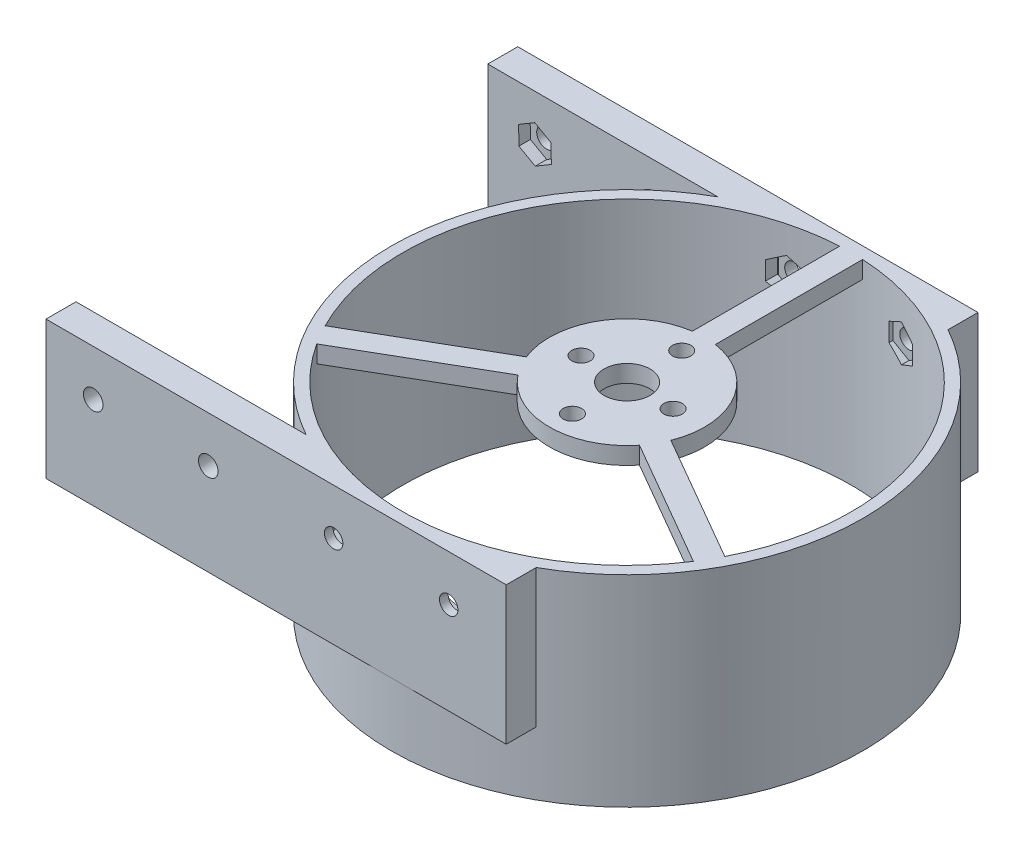
SolidWorks part; units mm, degrees
ref_plane "前视基准面" through (0, 0, 0) normal (0, 0, 1) x (1, 0, 0)
ref_plane "上视基准面" through (0, 0, 0) normal (0, 1, 0) x (1, 0, 0)
ref_plane "右视基准面" through (0, 0, 0) normal (1, 0, 0) x (0, 0, -1)
sketch "草图1" plane through (0, 0, 0) normal (0, 1, 0) x (1, 0, 0)
  circle A0 centre (0, 0) radius 39
  circle A1 centre (0, 0) radius 41
  dimension "D1" = 78
  dimension "D2" = 2
extrude "凸台-拉伸1" add sketch "草图1" along normal blind 20
sketch "草图2" plane through (0, 20, 0) normal (0, 1, 0) x (1, 0, 0)
  line L0 (20, -41) -> (-20, -41)
  line L1 (-20, -41) -> (-20, -35.7911)
  line L2 (0, -41) -> (0, -31.4417) construction
  line L3 (20, -41) -> (20, -35.7911)
  line L4 (0, 0) -> (26.2566, 0) construction
  line L5 (20, 41) -> (20, 35.7911)
  line L6 (20, 41) -> (-20, 41)
  line L7 (-20, 41) -> (-20, 35.7911)
  circle A0 centre (0, 0) radius 41 construction
  arc A1 (-20, -35.7911) -> (20, -35.7911) centre (0, 0) ccw
  arc A2 (-20, 35.7911) -> (20, 35.7911) centre (0, 0) cw
  circle M5 centre (0, 0) radius 41
extrude "凸台-拉伸2" add sketch "草图2" against normal blind 14 contours L1 L0 M5 | L0 L3 M5 region at (15.0657, 20, 39.4559) region at (-15.0657, 20, 39.4559)
sketch "草图3" plane through (0, 20, 0) normal (0, 1, 0) x (1, 0, 0)
  line L0 (-2, 38.9487) -> (-2, 13.351)
  line L1 (0, 39) -> (0, 13.5) construction
  line L2 (2, 38.9487) -> (2, 13.351)
  line L3 (34.7305, -17.7423) -> (12.5623, -4.9435)
  line L4 (32.7305, -21.2064) -> (10.5623, -8.4076)
  line L5 (-32.7305, -21.2064) -> (-10.5623, -8.4076)
  line L6 (-34.7305, -17.7423) -> (-12.5623, -4.9435)
  circle A0 centre (0, 0) radius 4
  circle A1 centre (-8, 0) radius 1.6
  circle A2 centre (8, 0) radius 1.6
  arc A3 (-10.5623, -8.4076) -> (10.5623, -8.4076) centre (0, 0) ccw
  circle A4 centre (0, 0) radius 39 construction
  arc A5 (2, 38.9487) -> (-2, 38.9487) centre (0, 0) ccw
  arc A6 (32.7305, -21.2064) -> (34.7305, -17.7423) centre (0, 0) ccw
  arc A7 (-34.7305, -17.7423) -> (-32.7305, -21.2064) centre (0, 0) ccw
  arc A8 (-2, 13.351) -> (-12.5623, -4.9435) centre (0, 0) ccw
  arc A9 (12.5623, -4.9435) -> (2, 13.351) centre (0, 0) ccw
  point P28 (0, 0)
  dimension "D1" = 8
  dimension "D2" = 3.2
  dimension "D3" = 8
  dimension "D4" = 3.2
  dimension "D5" = 8
  dimension "D6" = 27
  dimension "D7" = 2
  dimension "D8" = 3
extrude "凸台-拉伸3" add sketch "草图3" against normal blind 3
sketch "草图4" plane through (0, 0, 41) normal (0, 0, 1) x (1, 0, 0)
  line L0 (20, 20) -> (-20, 20) construction
  line L1 (-10, 8.7668) -> (-7.2, 10.3834)
  line L2 (-7.2, 10.3834) -> (-7.2, 13.6166)
  line L3 (-7.2, 13.6166) -> (-10, 15.2332)
  line L4 (-10, 15.2332) -> (-12.8, 13.6166)
  line L5 (-12.8, 13.6166) -> (-12.8, 10.3834)
  line L6 (-12.8, 10.3834) -> (-10, 8.7668)
  line L7 (0, 0) -> (0, -4.0742) construction
  line L8 (12.8, 10.3834) -> (10, 8.7668)
  line L9 (12.8, 13.6166) -> (12.8, 10.3834)
  line L10 (10, 15.2332) -> (12.8, 13.6166)
  line L11 (7.2, 13.6166) -> (10, 15.2332)
  line L12 (7.2, 10.3834) -> (7.2, 13.6166)
  line L13 (10, 8.7668) -> (7.2, 10.3834)
  circle A0 centre (-10, 12) radius 2.8 construction
  dimension "D1" = 5.6
  dimension "D2" = 10
  dimension "D3" = 8
sketch "草图7" plane through (0, 6, 0) normal (0, -1, 0) x (1, 0, 0)
  line L2 (-20, 41) -> (-20, 35.7911)
  line L3 (0, 41) -> (-20, 41)
  line L4 (-20, 41) -> (-20, 35.7911)
  line L5 (0, 41) -> (-20, 41)
  line L6 (20, 41) -> (0, 41)
  line L7 (20, 35.7911) -> (20, 41)
  line L8 (20, 41) -> (0, 41)
  line L9 (20, 35.7911) -> (20, 41)
  arc A1 (0, 41) -> (-20, 35.7911) centre (0, 0) ccw
  arc A2 (0, 41) -> (-20, 35.7911) centre (0, 0) ccw
  arc A3 (20, 35.7911) -> (0, 41) centre (0, 0) ccw
  arc A4 (20, 35.7911) -> (0, 41) centre (0, 0) ccw
  line M7 (-20, 41) -> (-20, 35.7911)
  arc M8 (-20, 35.7911) -> (0, 41) centre (0, 0) cw
  line M9 (0, 41) -> (-20, 41)
  dimension "D1" = 0
  dimension "D2" = 0
extrude "切除-拉伸3" cut sketch "草图7" against normal blind 3 contours M9 M7 M8 | A4 L9 L8 region at (-15.0657, 6, 39.4559) region at (15.0657, 6, 39.4559)
sketch "草图9" plane through (0, 0, 0) normal (0, -1, 0) x (1, 0, 0)
sketch "草图10" plane through (0, 0, 0) normal (0, -1, 0) x (1, 0, 0)
sketch "草图11" plane through (0, 0, 0) normal (0, -1, 0) x (1, 0, 0)
sketch "草图12" plane through (0, 0, 0) normal (0, -1, 0) x (1, 0, 0)
  circle A2 centre (0.1979, 0.0085) radius 41.1981
extrude "凸台-拉伸5" add sketch "草图1<2>" along normal blind 10 and the other way blind 15
sketch "草图1<2>" plane through (0, 0, 0) normal (0, 1, 0) x (1, 0, 0) same geometry as "草图1"
extrude "凸台-拉伸7" add sketch "草图7<4>" along normal blind 10
sketch "草图7<4>" plane through (0, 6, 0) normal (0, -1, 0) x (1, 0, 0) same geometry as "草图7"
extrude "凸台-拉伸8" add sketch "草图7<5>" along normal blind 10 and the other way blind 5 contours M9 M7 M8 | A4 L9 L8 region at (-15.0657, 6, 39.4559) region at (15.0657, 6, 39.4559)
sketch "草图7<5>" plane through (0, 6, 0) normal (0, -1, 0) x (1, 0, 0) same geometry as "草图7"
extrude "切除-拉伸4" cut sketch "草图4" against normal blind 80
sketch "草图20" plane through (0, 20, 0) normal (0, 1, 0) x (1, 0, 0)
  line L0 (-20, 35.7911) -> (-20, 41)
  line L1 (-20, 41) -> (20, 41)
  line L2 (20, 41) -> (20, 35.7911)
  arc A0 (-20, 35.7911) -> (20, 35.7911) centre (0, 0) cw
  arc M13 (20, -35.7911) -> (-20, -35.7911) centre (0, 0) ccw
extrude "凸台-拉伸10" add sketch "草图20" against normal blind 24 contours L2 L1 M13 | L1 L0 M13 | L1 L2 A0 L0 region at (15.0657, 20, -39.4559) region at (-15.0657, 20, -39.4559)
extrude "凸台-拉伸9" add sketch "草图4<3>" along normal blind 10 and the other way blind 1.5
sketch "草图4<3>" plane through (0, 0, 41) normal (0, 0, 1) x (1, 0, 0) same geometry as "草图4"
sketch "草图13" plane through (0, 0, 51) normal (0, 0, 1) x (1, 0, 0)
  line L0 (10, 15.2332) -> (7.2, 13.6166)
  line L1 (7.2, 13.6166) -> (7.2, 10.3834)
  line L2 (7.2, 10.3834) -> (10, 8.7668)
  line L3 (10, 8.7668) -> (12.8, 10.3834)
  line L4 (12.8, 10.3834) -> (12.8, 13.6166)
  line L5 (12.8, 13.6166) -> (10, 15.2332)
  line L6 (-10, 15.2332) -> (-12.8, 13.6166)
  line L7 (-12.8, 13.6166) -> (-12.8, 10.3834)
  line L8 (-12.8, 10.3834) -> (-10, 8.7668)
  line L9 (-10, 8.7668) -> (-7.2, 10.3834)
  line L10 (-7.2, 10.3834) -> (-7.2, 13.6166)
  line L11 (-7.2, 13.6166) -> (-10, 15.2332)
extrude "切除-拉伸6" cut sketch "草图13" against normal blind 10
sketch "草图16" plane through (0, 0, 41) normal (0, 0, 1) x (1, 0, 0)
  line L1 (0, 0) -> (0, 20) construction
  line L2 (20, 20) -> (-20, 20) construction
  line L3 (20, 20) -> (-20, 20) construction
  circle A0 centre (-10, 12) radius 1.6
  circle A1 centre (10, 12) radius 1.6
  dimension "D1" = 20
  dimension "D2" = 10
  dimension "D3" = 8
extrude "切除-拉伸7" cut sketch "草图16" against normal blind 103
sketch "草图18" plane through (0, 20, 0) normal (0, 1, 0) x (1, 0, 0)
  circle A1 centre (0, 9.5) radius 1.6
  circle A2 centre (0, -9.5) radius 1.6
  dimension "D1" = 19
extrude "切除-拉伸8" cut sketch "草图18" against normal blind 10 contours A1
extrude "切除-拉伸9" cut sketch "草图18<4>" against normal blind 10
sketch "草图18<4>" plane through (0, 20, 0) normal (0, 1, 0) x (1, 0, 0) same geometry as "草图18"
sketch "草图21" plane through (-20, 0, 0) normal (-1, 0, 0) x (0, 0, 1)
  line L1 (35.7911, 20) -> (41, 20)
  line L2 (35.7911, 20) -> (35.7911, -4)
  line L3 (35.7911, -4) -> (41, -4)
  line L4 (41, 20) -> (41, -4)
extrude "凸台-拉伸11" add sketch "草图21" along normal blind 40
sketch3d "3D草图1"
  point P0 (-60, 4.7339, 38.0971)
sketch "草图22" plane through (-20, 0, 0) normal (-1, 0, 0) x (0, 0, 1)
  line L1 (-41, 20) -> (-35.7911, 20)
  line L2 (-41, 20) -> (-41, -4)
  line L3 (-41, -4) -> (-35.7911, -4)
  line L4 (-35.7911, 20) -> (-35.7911, -4)
extrude "凸台-拉伸12" add sketch "草图22" along normal blind 40
ref_plane "基准面2" through (0, 0, 0) normal (0, 0, -1) x (-1, 0, 0)
sketch "草图23" plane through (0, 0, 41) normal (0, 0, 1) x (1, 0, 0)
  line L0 (-10, 12) -> (10, 12) construction
  circle A0 centre (-51.7964, 12) radius 1.7
  circle A1 centre (-31.7964, 12) radius 1.7
  dimension "D1" = 20
extrude "切除-拉伸10" cut sketch "草图23" against normal blind 10
sketch "草图24" plane through (0, 0, 35.7911) normal (0, 0, -1) x (-1, 0, 0)
  line L1 (41.7964, 12) -> (41.7964, 7.7214) construction
  line L10 (51.7964, 12) -> (51.7964, 22.173) construction
  line L11 (31.8332, 8.7456) -> (28.9964, 10.341)
  line L12 (54.5964, 10.341) -> (54.6332, 13.5954)
  line L13 (54.6332, 13.5954) -> (51.8332, 15.2544)
  line L14 (51.8332, 15.2544) -> (48.9964, 13.659)
  line L15 (48.9964, 13.659) -> (48.9597, 10.4046)
  line L16 (48.9597, 10.4046) -> (51.7597, 8.7456)
  line L17 (51.7597, 8.7456) -> (54.5964, 10.341)
  line L18 (28.9964, 10.341) -> (28.9597, 13.5954)
  line L19 (28.9597, 13.5954) -> (31.7597, 15.2544)
  line L20 (31.7597, 15.2544) -> (34.5964, 13.659)
  line L21 (34.5964, 13.659) -> (34.6332, 10.4046)
  line L22 (34.6332, 10.4046) -> (31.8332, 8.7456)
  circle M7 centre (51.7964, 12) radius 1.7
  circle M8 centre (31.7964, 12) radius 1.7
extrude "切除-拉伸11" cut sketch "草图24" against normal blind 2 contours M7 | M8 region at (-30.4571, 9.6186, 35.7911) region at (-53.1357, 9.6186, 35.7911)
mirror "镜向1" about plane through (0, 0, 0) normal (0, 0, -1) of "切除-拉伸11"
mirror "镜向2" about plane through (0, 0, 0) normal (0, 0, -1) of "切除-拉伸10", "镜向1", "切除-拉伸11"
